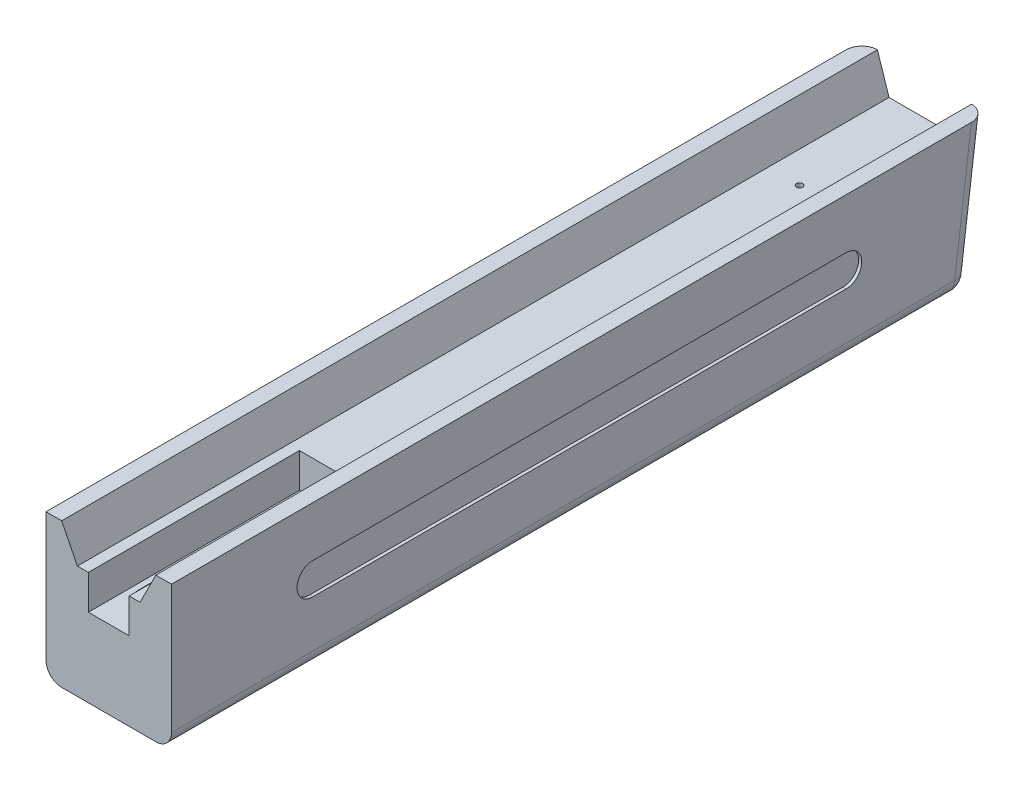
SolidWorks part; units mm, degrees
ref_plane "Front Plane" through (0, 0, 0) normal (0, 0, 1) x (1, 0, 0)
ref_plane "Top Plane" through (0, 0, 0) normal (0, 1, 0) x (1, 0, 0)
ref_plane "Right Plane" through (0, 0, 0) normal (1, 0, 0) x (0, 0, -1)
sketch "Sketch1" plane through (0, 0, 0) normal (0, 0, 1) x (1, 0, 0)
  line L0 (0, 0) -> (0, 46)
  line L1 (0, 46) -> (40, 46)
  line L2 (40, 46) -> (40, 0)
  line L3 (40, 0) -> (0, 0)
  dimension "D1" = 46
  dimension "D2" = 40
extrude "Boss-Extrude1" add sketch "Sketch1" along normal blind 260
sketch "Sketch2" plane through (0, 0, 260) normal (0, 0, 1) x (1, 0, 0)
  line L0 (10, 36) -> (30, 36)
  line L1 (0, 46) -> (0, 0) construction
  line L3 (10, 36) -> (5, 46)
  line L4 (40, 46) -> (0, 46) construction
  line L5 (30, 36) -> (35, 46)
  line L6 (5, 46) -> (35, 46)
  dimension "D1" = 20
  dimension "D2" = 10
  dimension "D3" = 5
  dimension "D4" = 5
  dimension "D5" = 10
extrude "Cut-Extrude1" cut sketch "Sketch2" against normal through all
sketch "Sketch3" plane through (0, 0, 260) normal (0, 0, 1) x (1, 0, 0)
  line L0 (13.5, 36) -> (13.5, 25)
  line L1 (10, 36) -> (30, 36) construction
  line L2 (13.5, 25) -> (26.5, 25)
  line L3 (26.5, 25) -> (26.5, 36)
  line L4 (13.5, 36) -> (26.5, 36)
  point P4 (26.5, 30.5)
  dimension "D1" = 3.5
  dimension "D2" = 13
  dimension "D3" = 11
extrude "Cut-Extrude2" cut sketch "Sketch3" against normal blind 67.275
sketch "Sketch4" plane through (0, 0, 0) normal (0, -1, 0) x (1, 0, 0)
  line L4 (28.863, 252.2108) -> (28.863, 229)
  line L5 (8.863, 252.2108) -> (8.863, 229)
  arc A2 (8.863, 252.2108) -> (28.863, 252.2108) centre (18.863, 237.8494) cw
  arc A3 (28.863, 229) -> (8.863, 229) centre (18.863, 229) cw
extrude "Cut-Extrude3" cut sketch "Sketch4" against normal blind 20
sketch "Sketch5" plane through (0, 20, 0) normal (0, -1, 0) x (1, 0, 0)
  line L0 (18.863, 246) -> (18.863, 229) construction
  line L1 (22.363, 246) -> (22.363, 229)
  line L2 (15.363, 246) -> (15.363, 229)
  line L3 (0, 260) -> (40, 260) construction
  line L6 (28.863, 229) -> (28.863, 252.2108) construction
  arc A0 (22.363, 246) -> (15.363, 246) centre (18.863, 246) ccw
  arc A1 (15.363, 229) -> (22.363, 229) centre (18.863, 229) ccw
  point P2 (18.863, 237.5)
  dimension "D1" = 8.5
  dimension "D2" = 22.5
  dimension "D3" = 7
  dimension "D4" = 10
extrude "Cut-Extrude4" cut sketch "Sketch5" against normal through all
fillet "Fillet2" radius 5 1 edges at (0, 0, 130)
sketch "Sketch6" plane through (0, 0, 0) normal (0, -1, 0) x (1, 0, 0)
  line L0 (5, 260) -> (40, 260) construction
  line L1 (0, 0) -> (0, 260) construction
  circle A0 centre (20, 202) radius 4
  dimension "D1" = 58
  dimension "D3" = 8
  dimension "D2" = 20
extrude "Cut-Extrude5" cut sketch "Sketch6" against normal blind 4
sketch "Sketch7" plane through (0, 4, 0) normal (0, -1, 0) x (1, 0, 0)
  circle A0 centre (20, 202) radius 3.5
  dimension "D1" = 7
extrude "Cut-Extrude6" cut sketch "Sketch7" against normal through all
sketch "Sketch8" plane through (40, 0, 0) normal (1, 0, 0) x (0, 0, -1)
  line L0 (-215, 25) -> (-45, 25) construction
  line L1 (-215, 30) -> (-45, 30)
  line L2 (-215, 20) -> (-45, 20)
  line L3 (-260, 0) -> (-260, 46) construction
  line L4 (-260, 46) -> (0, 46) construction
  arc A0 (-215, 30) -> (-215, 20) centre (-215, 25) ccw
  arc A1 (-45, 20) -> (-45, 30) centre (-45, 25) ccw
  point P2 (-130, 25)
  dimension "D4" = 21
  dimension "D1" = 10
  dimension "D2" = 45
  dimension "D3" = 170
extrude "Cut-Extrude7" cut sketch "Sketch8" against normal blind 1
sketch "Sketch9" plane through (0, 0, 0) normal (-1, 0, 0) x (0, 0, 1)
  line L0 (45, 25) -> (215, 25) construction
  line L1 (45, 30) -> (215, 30)
  line L2 (45, 20) -> (215, 20)
  line L3 (260, 46) -> (260, 5) construction
  line L4 (260, 46) -> (0, 46) construction
  arc A0 (45, 30) -> (45, 20) centre (45, 25) ccw
  arc A1 (215, 20) -> (215, 30) centre (215, 25) ccw
  point P2 (130, 25)
  dimension "D1" = 45
  dimension "D2" = 170
  dimension "D3" = 10
  dimension "D4" = 21
extrude "Cut-Extrude8" cut sketch "Sketch9" against normal blind 1
sketch "Sketch10" plane through (0, 36, 0) normal (0, 1, 0) x (1, 0, 0)
  line L0 (13.5, -260) -> (26.5, -260) construction
  line L1 (0, -260) -> (0, 0) construction
  circle A0 centre (20, -39.815) radius 1
  dimension "D2" = 2
  dimension "D1" = 220.185
  dimension "D3" = 20
extrude "Cut-Extrude9" cut sketch "Sketch10" against normal blind 5
sketch "Sketch11" plane through (40, 0, 0) normal (1, 0, 0) x (0, 0, -1)
  line L0 (0, 46) -> (-6, 0)
  line L1 (-260, 0) -> (0, 0) construction
  line L2 (-6, 0) -> (9.0551, 0)
  line L3 (9.0551, 0) -> (9.0551, 46)
  line L4 (9.0551, 46) -> (0, 46)
  dimension "D1" = 6
extrude "Cut-Extrude10" cut sketch "Sketch11" against normal through all
fillet "Fillet4" radius 5 1 edges at (40, 0, 133)
fillet "Fillet6" radius 5 5 edges at (40, 25.5, 2.6739) (38.5355, 1.4645, 5.809) (20, 0, 6) (1.4645, 1.4645, 5.809) (0, 25.5, 2.6739)
